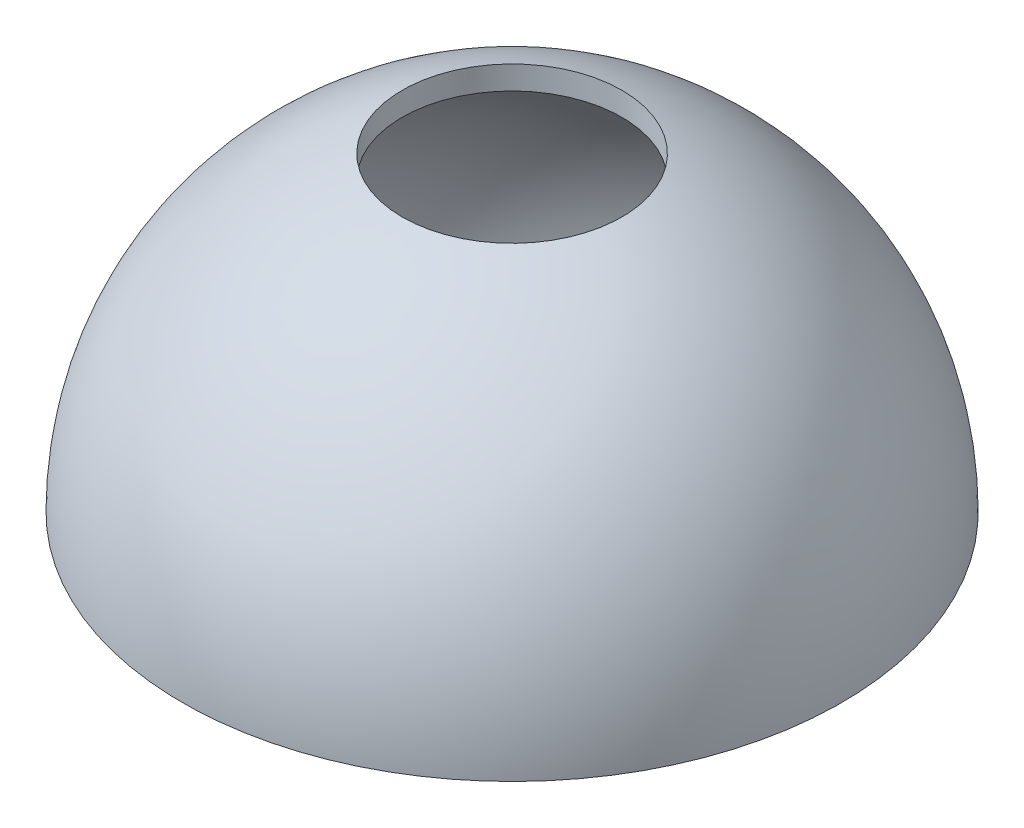
SolidWorks part; units mm, degrees
ref_plane "Front Plane" through (0, 0, 0) normal (0, 0, 1) x (1, 0, 0)
ref_plane "Top Plane" through (0, 0, 0) normal (0, 1, 0) x (1, 0, 0)
ref_plane "Right Plane" through (0, 0, 0) normal (1, 0, 0) x (0, 0, -1)
sketch "Sketch1" plane through (0, 0, 0) normal (0, 0, 1) x (1, 0, 0)
  line L0 (0, 0) -> (0, 150)
  line L1 (0, 0) -> (-150, 0)
  arc A0 (-150, 0) -> (0, 150) centre (0, 0) cw
  dimension "D1" = 150
revolve "Revolve1" add sketch "Sketch1" angle 360 about L0
shell "Shell1" thickness 10 removed face at (0, 0, -150)
sketch "Sketch2" plane through (0, 0, 0) normal (0, 1, 0) x (1, 0, 0)
  circle A0 centre (0, 0) radius 50
  dimension "D1" = 100
extrude "Cut-Extrude3" cut sketch "Sketch2" against normal through all and the other way through all
